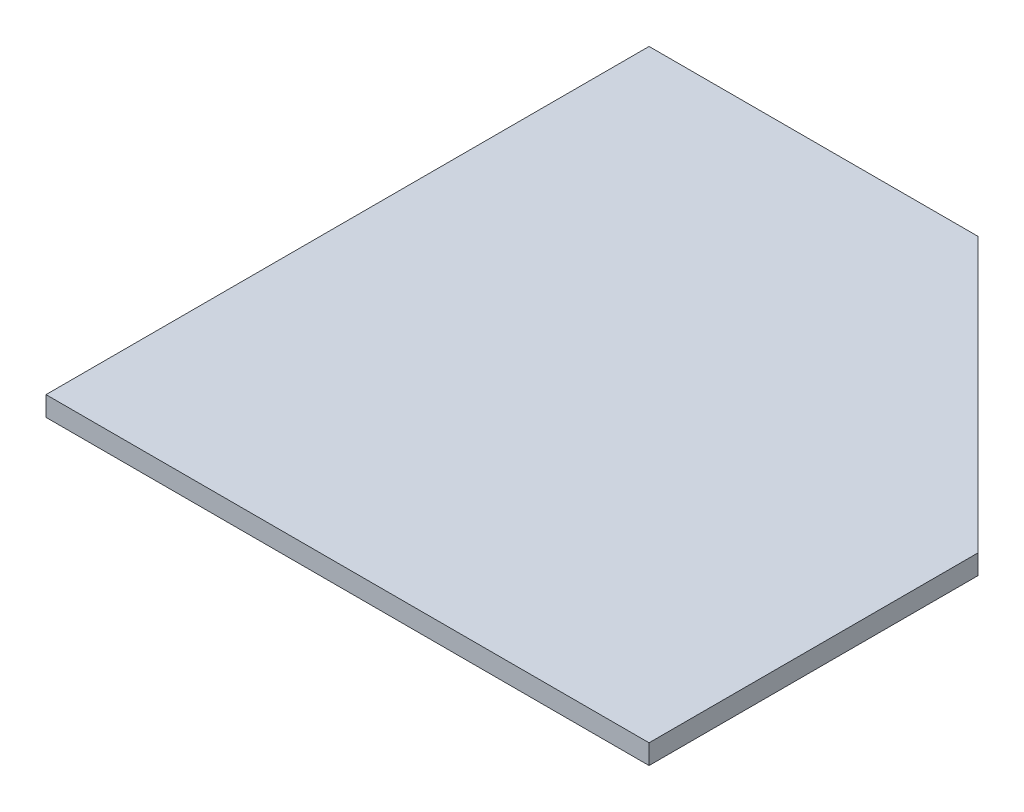
SolidWorks part; units mm, degrees
ref_plane "Спереди" through (0, 0, 0) normal (0, 0, 1) x (1, 0, 0)
ref_plane "Сверху" through (0, 0, 0) normal (0, 1, 0) x (1, 0, 0)
ref_plane "Справа" through (0, 0, 0) normal (1, 0, 0) x (0, 0, -1)
sketch "Эскиз1" plane through (0, 0, 0) normal (0, 1, 0) x (1, 0, 0)
  line L0 (0, 0) -> (0, 550)
  line L1 (0, 550) -> (300, 550)
  line L4 (550, 300) -> (550, 0)
  line L5 (550, 0) -> (0, 0)
  line L6 (300, 550) -> (550, 300)
  point P3 (0, 0)
extrude "Бобышка-Вытянуть1" add sketch "Эскиз1" along normal blind 18
